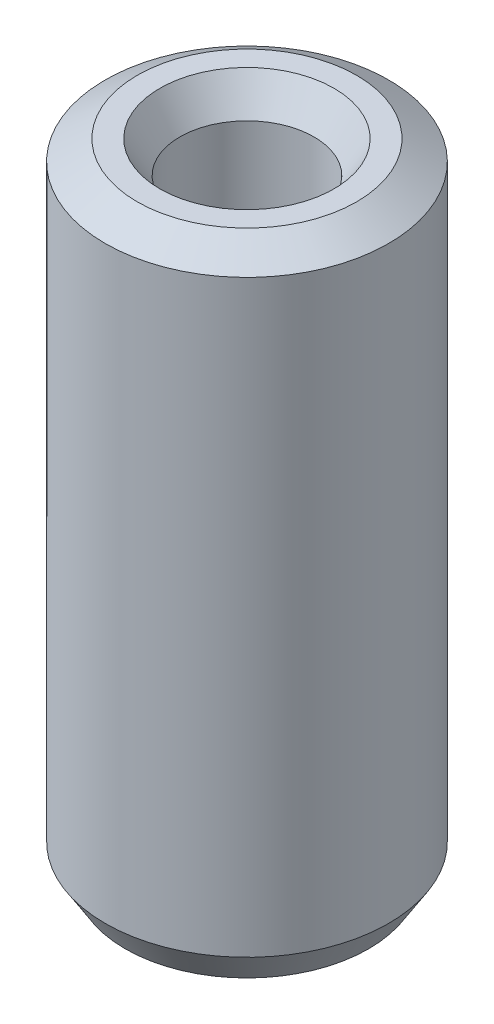
SolidWorks part; units mm, degrees
ref_plane "Front Plane" through (0, 0, 0) normal (0, 0, 1) x (1, 0, 0)
ref_plane "Top Plane" through (0, 0, 0) normal (0, 1, 0) x (1, 0, 0)
ref_plane "Right Plane" through (0, 0, 0) normal (1, 0, 0) x (0, 0, -1)
sketch "Sketch1" plane through (0, 0, 0) normal (0, 1, 0) x (1, 0, 0)
  circle A0 centre (0, 0) radius 7.5
  dimension "SLEEVE_OD" = 15
extrude "Boss-Extrude1" add sketch "Sketch1" along normal blind 33.92
sketch "Sketch2" plane through (0, 0, 0) normal (0, 1, 0) x (1, 0, 0)
  circle A0 centre (0, 0) radius 3.5506
  dimension "BORE_D" = 7.1013
extrude "Cut-Extrude1" cut sketch "Sketch2" along normal through all
chamfer "Chamfer1" distance 1.0602 angle 57.998 4 edges at (0, 33.92, 3.5506) (0, 0, 3.5506) (0, 0, 7.5) (0, 33.92, 7.5) first distance on face at (0, 33.92, 3.5506) first distance on face at (0, 0, 3.5506) first distance on face at (0, 33.92, 7.5)
